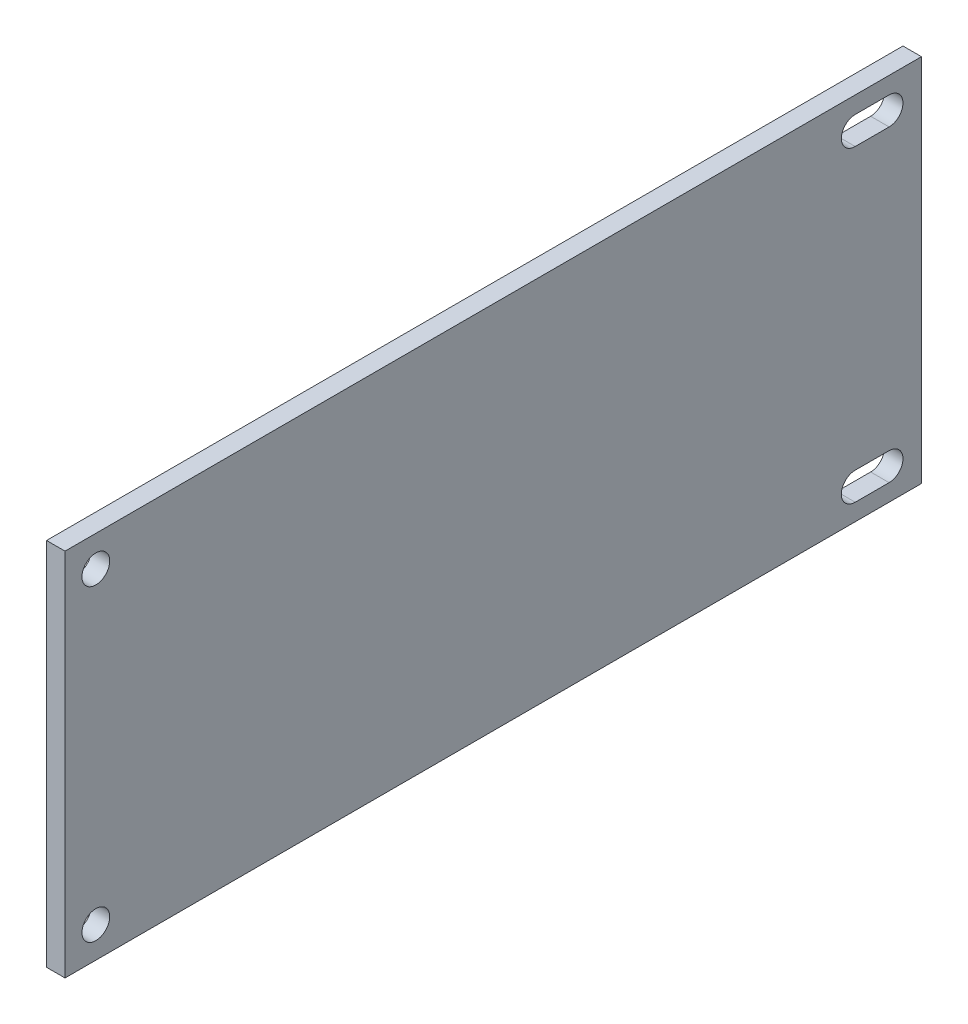
SolidWorks part; units mm, degrees
material "1060 合金"
ref_plane "前视基准面" through (0, 0, 0) normal (0, 0, 1) x (1, 0, 0)
ref_plane "上视基准面" through (0, 0, 0) normal (0, 1, 0) x (1, 0, 0)
ref_plane "右视基准面" through (0, 0, 0) normal (1, 0, 0) x (0, 0, -1)
sketch "草图1" plane through (0, 0, 0) normal (1, 0, 0) x (0, 0, -1)
  line L1 (139, 60) -> (0, 60)
  line L2 (139, 60) -> (139, 0)
  line L3 (139, 0) -> (0, 0)
  line L4 (0, 60) -> (0, 0)
  line L5 (139, 60) -> (0, 0) construction
  line L6 (139, 0) -> (0, 60) construction
  point P0 (69.5, 30)
  dimension "D2" = 60
  dimension "D3" = 139
extrude "凸台-拉伸1" add sketch "草图1" along normal mid plane 3
hole_wizard "M4 间隙孔1" positions "草图3" profile "草图2" hole size "M4" standard "GB" end condition through all
sketch "草图3" plane through (1.5, 0, 0) normal (1, 0, 0) x (0, 0, -1)
  line L0 (0, 60) -> (0, 0) construction
  line L1 (0, 30) -> (149.6179, 30) construction
  point P0 (5, 55)
  point P2 (5, 5)
  dimension "D2" = 50
  dimension "D3" = 5
sketch "草图2" plane through (1.5, 55, -5) normal (0, 1, 0) x (0, 0, -1)
  line L0 (0, 0) -> (0, 3)
  line L1 (0, 3) -> (2.25, 3)
  line L2 (2.25, 3) -> (2.25, 0)
  line L5 (2.25, 0) -> (0, 0)
  line L11 (0, -6.35) -> (0, 107.95) construction
  dimension "通孔孔直径" = 4.5
  dimension "通孔孔深度" = 3
hole_wizard "M4 间隙槽口1" positions "草图5" profile "草图4" size "M4" standard "GB" slot yes end condition through all
sketch "草图5" plane through (1.5, 0, 0) normal (1, 0, 0) x (0, 0, -1)
  line L0 (0, 30) -> (152.085, 30) construction
  line L1 (0, 60) -> (0, 0) construction
  line L4 (5, 55) -> (131, 55) construction
  line L5 (136, 55) -> (126, 55) construction
  point P9 (131, 55)
  point P22 (131, 5)
  dimension "D1" = 126
  dimension "D2" = 10
sketch "草图4" plane through (1.5, 55, -131) normal (0, 1, 0) x (0, 0, -1)
  line L0 (0, 0) -> (0, 3)
  line L1 (0, 3) -> (2.25, 3)
  line L2 (2.25, 3) -> (2.25, 0)
  line L5 (2.25, 0) -> (0, 0)
  line L11 (0, -6.35) -> (0, 107.95) construction
  dimension "通孔孔直径" = 4.5
  dimension "通孔孔深度" = 3
